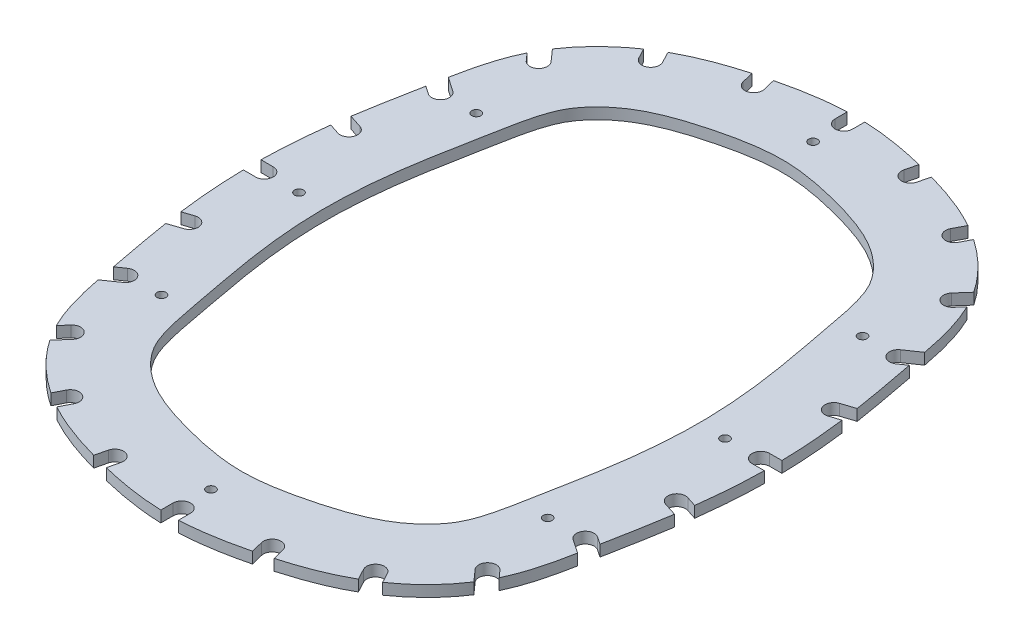
SolidWorks part; units mm, degrees
ref_plane "Front Plane" through (0, 0, 0) normal (0, 0, 1) x (1, 0, 0)
ref_plane "Top Plane" through (0, 0, 0) normal (0, 1, 0) x (1, 0, 0)
ref_plane "Right Plane" through (0, 0, 0) normal (1, 0, 0) x (0, 0, -1)
sketch "MainControlPoints" plane through (0, 0, 0) normal (0, 1, 0) x (1, 0, 0)
  line L1 (0, 188.5) -> (0, 0) construction
  line L2 (-44.5, 181.8105) -> (44.5, 181.8105) construction
  line L9 (-141, 0) -> (141, 0) construction
  line L10 (-86.25, 165.0195) -> (86.25, 165.0195) construction
  line L11 (-117.5, 132.6399) -> (117.5, 132.6399) construction
  line L12 (-130, 89.4108) -> (130, 89.4108) construction
  line L13 (-137.75, 45.0832) -> (137.75, 45.0832) construction
  spline S0 degree 3 poles (-44.8235, 182.8439) (0, 191.3281) (44.8235, 182.8439) (87.706, 168.1591) (121.8523, 134.6364) (129.8847, 89.1344) (138.6218, 45.2258) (142.1917, 0) (138.6218, -45.2258) (129.8847, -89.1344) (121.8523, -134.6364) (87.706, -168.1591) (44.8235, -182.8439) (0, -191.3281) (-44.8235, -182.8439) (-87.706, -168.1591) (-121.8523, -134.6364) (-129.8847, -89.1344) (-138.6218, -45.2258) (-142.1917, 0) (-138.6218, 45.2258) (-129.8847, 89.1344) (-121.8523, 134.6364) (-87.706, 168.1591) (-44.8235, 182.8439) (0, 191.3281) (44.8235, 182.8439) knots -0.124907 -0.083272 -0.041636 0 0.041636 0.083272 0.124907 0.166543 0.208179 0.25 0.291821 0.333457 0.375093 0.416728 0.458364 0.5 0.541636 0.583272 0.624907 0.666543 0.708179 0.75 0.791821 0.833457 0.875093 0.916728 0.958364 1 1.041636 1.083272 1.124907 only from (0, 188.5) to (0, 188.5)
  point P4 (0, 181.8105)
  point P7 (0, 0)
  point P8 (141, 0)
  point P9 (-141, 0)
  point P11 (44.5, 181.8105)
  point P14 (86.25, 165.0195)
  point P15 (0, 165.0195)
  point P16 (117.5, 132.6399)
  point P17 (130, 89.4108)
  point P18 (-44.5, 181.8105)
  point P19 (-86.25, 165.0195)
  point P20 (-117.5, 132.6399)
  point P23 (0, 132.6399)
  point P24 (137.75, 45.0832)
  point P25 (-130, 89.4108)
  point P26 (-137.75, 45.0832)
  point P27 (0, 188.5)
  point P30 (0, 89.4108)
  point P33 (0, 45.0832)
  point P34 (137.75, -45.0832)
  point P35 (130, -89.4108)
  point P36 (117.5, -132.6399)
  point P37 (86.25, -165.0195)
  point P38 (44.5, -181.8105)
  point P39 (0, -188.5)
  point P40 (-44.5, -181.8105)
  point P41 (-86.25, -165.0195)
  point P42 (-117.5, -132.6399)
  point P43 (-130, -89.4108)
  point P44 (-137.75, -45.0832)
  dimension "D3" = 282
  dimension "D2" = 188.5
  dimension "D5" = 45
  dimension "D6" = 45
  dimension "D1" = 89
  dimension "D4" = 172.5
  dimension "D7" = 45
  dimension "D8" = 235
  dimension "D9" = 45
  dimension "D10" = 260
  dimension "D11" = 45
  dimension "D12" = 275.5
ref_axis "Axis1" through (0, 0, -188.5) along (0, 1, 0)
ref_axis "Axis2" through (44.5, 0, -181.8105) along (0, 1, 0)
ref_axis "Axis3" through (86.25, 0, -165.0195) along (0, 1, 0)
ref_axis "Axis4" through (117.5, 0, -132.6399) along (0, 1, 0)
ref_axis "Axis5" through (130, 0, -89.4108) along (0, 1, 0)
ref_axis "Axis6" through (137.75, 0, -45.0832) along (0, 1, 0)
ref_axis "Axis7" through (141, 0, 0) along (0, 1, 0)
ref_axis "Axis8" through (137.75, 0, 45.0832) along (0, 1, 0)
ref_axis "Axis9" through (130, 0, 89.4108) along (0, 1, 0)
ref_axis "Axis10" through (117.5, 0, 132.6399) along (0, 1, 0)
ref_axis "Axis11" through (86.25, 0, 165.0195) along (0, 1, 0)
ref_axis "Axis12" through (44.5, 0, 181.8105) along (0, 1, 0)
ref_axis "Axis13" through (0, 0, 188.5) along (0, 1, 0)
ref_axis "Axis14" through (-44.5, 0, 181.8105) along (0, 1, 0)
ref_axis "Axis15" through (-86.25, 0, 165.0195) along (0, 1, 0)
ref_axis "Axis16" through (-117.5, 0, 132.6399) along (0, 1, 0)
ref_axis "Axis17" through (-130, 0, 89.4108) along (0, 1, 0)
ref_axis "Axis18" through (-137.75, 0, 45.0832) along (0, 1, 0)
ref_axis "Axis19" through (-141, 0, 0) along (0, 1, 0)
ref_axis "Axis20" through (-137.75, 0, -45.0832) along (0, 1, 0)
ref_axis "Axis21" through (-130, 0, -89.4108) along (0, 1, 0)
ref_axis "Axis22" through (-117.5, 0, -132.6399) along (0, 1, 0)
ref_axis "Axis23" through (-86.25, 0, -165.0195) along (0, 1, 0)
ref_axis "Axis24" through (-44.5, 0, -181.8105) along (0, 1, 0)
sketch "Sketch3" plane through (0, 0, 0) normal (0, 1, 0) x (1, 0, 0)
  spline S2 degree 3 poles (44.8235, 182.8439) (0, 191.3281) (-44.8235, 182.8439) (-87.706, 168.1591) (-121.8523, 134.6364) (-129.8847, 89.1344) (-138.6218, 45.2258) (-142.1917, 0) (-138.6218, -45.2258) (-129.8847, -89.1344) (-121.8523, -134.6364) (-87.706, -168.1591) (-44.8235, -182.8439) (0, -191.3281) (44.8235, -182.8439) (87.706, -168.1591) (121.8523, -134.6364) (129.8847, -89.1344) (138.6218, -45.2258) (142.1917, 0) (138.6218, 45.2258) (129.8847, 89.1344) (121.8523, 134.6364) (87.706, 168.1591) (44.8235, 182.8439) (0, 191.3281) (-44.8235, 182.8439) knots -0.124907 -0.083272 -0.041636 0 0.041636 0.083272 0.124907 0.166543 0.208179 0.25 0.291821 0.333457 0.375093 0.416728 0.458364 0.5 0.541636 0.583272 0.624907 0.666543 0.708179 0.75 0.791821 0.833457 0.875093 0.916728 0.958364 1 1.041636 1.083272 1.124907 only from (0, 188.5) to (0, 188.5)
  spline S3 degree 3 poles (44.8235, 182.8439) (0, 191.3281) (-44.8235, 182.8439) (-87.706, 168.1591) (-121.8523, 134.6364) (-129.8847, 89.1344) (-138.6218, 45.2258) (-142.1917, 0) (-138.6218, -45.2258) (-129.8847, -89.1344) (-121.8523, -134.6364) (-87.706, -168.1591) (-44.8235, -182.8439) (0, -191.3281) (44.8235, -182.8439) (87.706, -168.1591) (121.8523, -134.6364) (129.8847, -89.1344) (138.6218, -45.2258) (142.1917, 0) (138.6218, 45.2258) (129.8847, 89.1344) (121.8523, 134.6364) (87.706, 168.1591) (44.8235, 182.8439) (0, 191.3281) (-44.8235, 182.8439) knots -0.124907 -0.083272 -0.041636 0 0.041636 0.083272 0.124907 0.166543 0.208179 0.25 0.291821 0.333457 0.375093 0.416728 0.458364 0.5 0.541636 0.583272 0.624907 0.666543 0.708179 0.75 0.791821 0.833457 0.875093 0.916728 0.958364 1 1.041636 1.083272 1.124907 only from (0, 188.5) to (0, 188.5)
  dimension "D1" = 0
extrude "MainBody" add sketch "Sketch3" along normal blind 6.35
sketch "Sketch13" plane through (0, 6.35, 0) normal (0, 1, 0) x (1, 0, 0)
  spline S2 degree 3 poles (-0.0923, -195.5) (5.9061, -195.5) (11.7392, -195.085) (23.2981, -193.6453) (29.0237, -192.6199) (37.5559, -190.7615) (40.3905, -190.0886) (46.0447, -188.657) (48.8649, -187.9023) (53.0829, -186.6998) (54.4867, -186.2866) (57.2893, -185.4316) (58.6882, -184.9896) (62.8604, -183.6197) (65.6138, -182.6462) (73.7714, -179.5048) (79.0728, -177.1157) (86.7462, -172.933) (89.2575, -171.4385) (92.9463, -169.029) (94.1653, -168.1965) (96.5575, -166.4889) (97.7326, -165.6128) (101.1944, -162.9177) (103.4182, -161.032) (107.6923, -157.0772) (109.7427, -155.0081) (112.678, -151.7562) (113.633, -150.6474) (115.0284, -148.9451) (115.4873, -148.3711) (116.3925, -147.2097) (116.8393, -146.6213) (119.0306, -143.6582) (120.6466, -141.2209) (123.5916, -136.206) (124.9153, -133.6259) (127.2923, -128.3337) (128.3485, -125.623) (129.7723, -121.4785) (130.2202, -120.084) (131.0691, -117.272) (131.4694, -115.8571) (132.6042, -111.6095) (133.2755, -108.7656) (134.5145, -103.0626) (135.0819, -100.2036) (136.1775, -94.48) (136.707, -91.6156) (138.3251, -83.0265) (139.4215, -77.303) (141.5293, -65.8438) (142.5403, -60.108) (143.9035, -51.4821) (144.3323, -48.6031) (145.1247, -42.8358) (145.4885, -39.9475) (147.1362, -25.4811) (147.9101, -13.8294) (148.003, -0.6092) (148.0024, 0.8623) (147.9792, 3.8019) (147.9568, 5.2701) (147.8578, 9.6699) (147.7498, 12.5969) (147.3068, 21.3604) (146.8533, 27.1792) (145.6651, 38.7754) (144.9284, 44.5524) (143.2126, 56.0705) (142.2389, 61.8124) (140.1775, 73.2794) (139.0901, 79.0044) (137.4645, 87.5929) (136.9262, 90.4562) (135.8531, 96.1835) (135.3122, 99.0464) (133.5786, 107.6189) (132.2779, 113.3124) (130.1353, 120.3529) (129.6824, 121.7514) (128.7233, 124.5187) (128.2169, 125.8886) (126.6073, 129.9525) (125.4138, 132.6004) (122.7385, 137.7496) (121.2544, 140.2496) (118.8215, 143.8945) (117.9761, 145.0919) (116.2177, 147.4523) (115.3033, 148.6168) (112.4942, 152.0199) (110.5242, 154.1827) (106.4077, 158.3162) (104.2612, 160.2869) (99.8013, 164.0465) (97.4878, 165.8355) (93.8939, 168.384) (92.6724, 169.2128) (90.2027, 170.8151) (88.9554, 171.5879) (82.6598, 175.3171) (77.4348, 177.8708) (66.7035, 182.3362) (61.1969, 184.2476) (54.1978, 186.3725) (52.791, 186.7846) (49.9736, 187.5842) (48.5634, 187.9716) (44.3294, 189.1029) (41.5021, 189.818) (33.0032, 191.8167) (27.3144, 192.953) (15.8708, 194.6608) (10.1162, 195.2328) (1.4182, 195.5241) (-1.4925, 195.5238) (-7.3372, 195.3237) (-10.2708, 195.1267) (-14.6866, 194.6996) (-16.1609, 194.5352) (-19.0943, 194.1679) (-20.556, 193.9647) (-24.9277, 193.3015) (-27.824, 192.7881) (-36.4681, 191.071) (-42.1715, 189.6926) (-53.5026, 186.6371) (-59.1262, 184.9441) (-66.0624, 182.4605) (-67.445, 181.9454) (-70.1997, 180.8739) (-71.5737, 180.3168) (-75.6639, 178.5832) (-78.3432, 177.3468) (-83.5935, 174.6901) (-86.1644, 173.2698) (-91.1858, 170.2243) (-93.6357, 168.5985) (-97.2169, 166.0005) (-98.395, 165.108) (-100.7189, 163.2682) (-101.8655, 162.32) (-105.2234, 159.4186) (-107.3637, 157.4004) (-111.4418, 153.191) (-113.3796, 150.9998) (-117.0378, 146.4319) (-118.7583, 144.0551) (-121.1568, 140.3344) (-121.9259, 139.0681) (-123.0304, 137.1268) (-123.3898, 136.4736) (-124.087, 135.1618) (-124.4255, 134.5022) (-126.0692, 131.1868) (-127.2294, 128.4785) (-130.3408, 120.2205) (-131.9223, 114.5371) (-134.5909, 102.9918) (-135.6643, 97.1921) (-137.8355, 85.5987) (-138.9477, 79.8043) (-141.1029, 68.2094) (-142.1451, 62.4088) (-143.5618, 53.6948) (-144.0097, 50.788) (-144.8419, 44.9686) (-145.2255, 42.056) (-146.97, 27.4776) (-147.815, 15.7657) (-148.0521, -1.8942) (-147.9538, -7.7967) (-147.4225, -19.6316) (-146.9909, -25.5639) (-146.1143, -34.4827) (-145.7838, -37.4592) (-145.0527, -43.3941) (-144.6515, -46.3556) (-143.3516, -55.2244) (-142.36, -61.1163) (-140.253, -72.8796) (-139.1381, -78.7512) (-137.4708, -87.5593) (-136.9189, -90.496) (-135.8181, -96.3698) (-135.2627, -99.3053) (-133.4794, -108.0788) (-132.1352, -113.8842) (-129.4893, -122.4151) (-128.5024, -125.2292) (-126.8117, -129.3912) (-126.2131, -130.7686) (-125.2553, -132.818) (-124.9263, -133.498) (-124.2516, -134.843) (-123.9056, -135.5092) (-122.1306, -138.8075) (-120.5688, -141.343) (-117.1925, -146.2303) (-115.378, -148.582) (-111.5149, -153.1153) (-109.4647, -155.2983) (-105.1449, -159.494) (-102.9036, -161.4797) (-95.9543, -167.1259) (-91.0211, -170.4758) (-84.4967, -174.1698) (-83.1716, -174.8856) (-80.5028, -176.2632) (-79.1594, -176.925) (-75.1047, -178.8358) (-72.3686, -180.0105) (-64.0786, -183.2871) (-58.4429, -185.1422) (-49.8888, -187.6214) (-47.0211, -188.3984) (-41.2605, -189.8765) (-38.3664, -190.5739) (-32.5429, -191.862) (-29.6099, -192.4531) (-23.735, -193.4975) (-20.7901, -193.9515) (-14.8831, -194.699) (-11.9208, -194.9924) (-7.4624, -195.2928) (-5.9738, -195.3696) (-3.7367, -195.4473) (-2.6172, -195.4768) (-1.3092, -195.4942) (-0.6548, -195.4985) (-0.3742, -195.4995) (-0.1871, -195.4999) (-0.0923, -195.5) (5.9061, -195.5) (11.7392, -195.085) knots -0.000244 -0.000244 0 0 0.015625 0.015625 0.03125 0.03125 0.039063 0.039063 0.046875 0.046875 0.050781 0.050781 0.054688 0.054688 0.0625 0.0625 0.078125 0.078125 0.085938 0.085938 0.089844 0.089844 0.09375 0.09375 0.101563 0.101563 0.109375 0.109375 0.113281 0.113281 0.115234 0.115234 0.117188 0.117188 0.125 0.125 0.132813 0.132813 0.140625 0.140625 0.144531 0.144531 0.148438 0.148438 0.15625 0.15625 0.164063 0.164063 0.171875 0.171875 0.1875 0.1875 0.203125 0.203125 0.210938 0.210938 0.21875 0.21875 0.25 0.25 0.253906 0.253906 0.257813 0.257813 0.265625 0.265625 0.28125 0.28125 0.296875 0.296875 0.3125 0.3125 0.328125 0.328125 0.335938 0.335938 0.34375 0.34375 0.359375 0.359375 0.363281 0.363281 0.367188 0.367188 0.375 0.375 0.382813 0.382813 0.386719 0.386719 0.390625 0.390625 0.398438 0.398438 0.40625 0.40625 0.414063 0.414063 0.417969 0.417969 0.421875 0.421875 0.4375 0.4375 0.453125 0.453125 0.457031 0.457031 0.460938 0.460938 0.46875 0.46875 0.484375 0.484375 0.5 0.5 0.507813 0.507813 0.515625 0.515625 0.519531 0.519531 0.523438 0.523438 0.53125 0.53125 0.546875 0.546875 0.5625 0.5625 0.566406 0.566406 0.570313 0.570313 0.578125 0.578125 0.585938 0.585938 0.59375 0.59375 0.597656 0.597656 0.601563 0.601563 0.609375 0.609375 0.617188 0.617188 0.625 0.625 0.628906 0.628906 0.630859 0.630859 0.632813 0.632813 0.640625 0.640625 0.65625 0.65625 0.671875 0.671875 0.6875 0.6875 0.703125 0.703125 0.710937 0.710937 0.71875 0.71875 0.75 0.75 0.765625 0.765625 0.78125 0.78125 0.789062 0.789062 0.796875 0.796875 0.8125 0.8125 0.828125 0.828125 0.835937 0.835937 0.84375 0.84375 0.859375 0.859375 0.867187 0.867187 0.871094 0.871094 0.873047 0.873047 0.875 0.875 0.882812 0.882812 0.890625 0.890625 0.898437 0.898437 0.90625 0.90625 0.921875 0.921875 0.925781 0.925781 0.929687 0.929687 0.9375 0.9375 0.953125 0.953125 0.960937 0.960937 0.96875 0.96875 0.976562 0.976562 0.984375 0.984375 0.992188 0.992188 0.996094 0.996094 0.998047 0.999023 0.999512 0.999756 0.999756 1 1 1.015625 1.015625 1.03125 only from (0, -195.5) to (0, -195.5)
  spline S3 degree 3 poles (-0.0923, -195.5) (5.9061, -195.5) (11.7392, -195.085) (23.2981, -193.6453) (29.0237, -192.6199) (37.5559, -190.7615) (40.3905, -190.0886) (46.0447, -188.657) (48.8649, -187.9023) (53.0829, -186.6998) (54.4867, -186.2866) (57.2893, -185.4316) (58.6882, -184.9896) (62.8604, -183.6197) (65.6138, -182.6462) (73.7714, -179.5048) (79.0728, -177.1157) (86.7462, -172.933) (89.2575, -171.4385) (92.9463, -169.029) (94.1653, -168.1965) (96.5575, -166.4889) (97.7326, -165.6128) (101.1944, -162.9177) (103.4182, -161.032) (107.6923, -157.0772) (109.7427, -155.0081) (112.678, -151.7562) (113.633, -150.6474) (115.0284, -148.9451) (115.4873, -148.3711) (116.3925, -147.2097) (116.8393, -146.6213) (119.0306, -143.6582) (120.6466, -141.2209) (123.5916, -136.206) (124.9153, -133.6259) (127.2923, -128.3337) (128.3485, -125.623) (129.7723, -121.4785) (130.2202, -120.084) (131.0691, -117.272) (131.4694, -115.8571) (132.6042, -111.6095) (133.2755, -108.7656) (134.5145, -103.0626) (135.0819, -100.2036) (136.1775, -94.48) (136.707, -91.6156) (138.3251, -83.0265) (139.4215, -77.303) (141.5293, -65.8438) (142.5403, -60.108) (143.9035, -51.4821) (144.3323, -48.6031) (145.1247, -42.8358) (145.4885, -39.9475) (147.1362, -25.4811) (147.9101, -13.8294) (148.003, -0.6092) (148.0024, 0.8623) (147.9792, 3.8019) (147.9568, 5.2701) (147.8578, 9.6699) (147.7498, 12.5969) (147.3068, 21.3604) (146.8533, 27.1792) (145.6651, 38.7754) (144.9284, 44.5524) (143.2126, 56.0705) (142.2389, 61.8124) (140.1775, 73.2794) (139.0901, 79.0044) (137.4645, 87.5929) (136.9262, 90.4562) (135.8531, 96.1835) (135.3122, 99.0464) (133.5786, 107.6189) (132.2779, 113.3124) (130.1353, 120.3529) (129.6824, 121.7514) (128.7233, 124.5187) (128.2169, 125.8886) (126.6073, 129.9525) (125.4138, 132.6004) (122.7385, 137.7496) (121.2544, 140.2496) (118.8215, 143.8945) (117.9761, 145.0919) (116.2177, 147.4523) (115.3033, 148.6168) (112.4942, 152.0199) (110.5242, 154.1827) (106.4077, 158.3162) (104.2612, 160.2869) (99.8013, 164.0465) (97.4878, 165.8355) (93.8939, 168.384) (92.6724, 169.2128) (90.2027, 170.8151) (88.9554, 171.5879) (82.6598, 175.3171) (77.4348, 177.8708) (66.7035, 182.3362) (61.1969, 184.2476) (54.1978, 186.3725) (52.791, 186.7846) (49.9736, 187.5842) (48.5634, 187.9716) (44.3294, 189.1029) (41.5021, 189.818) (33.0032, 191.8167) (27.3144, 192.953) (15.8708, 194.6608) (10.1162, 195.2328) (1.4182, 195.5241) (-1.4925, 195.5238) (-7.3372, 195.3237) (-10.2708, 195.1267) (-14.6866, 194.6996) (-16.1609, 194.5352) (-19.0943, 194.1679) (-20.556, 193.9647) (-24.9277, 193.3015) (-27.824, 192.7881) (-36.4681, 191.071) (-42.1715, 189.6926) (-53.5026, 186.6371) (-59.1262, 184.9441) (-66.0624, 182.4605) (-67.445, 181.9454) (-70.1997, 180.8739) (-71.5737, 180.3168) (-75.6639, 178.5832) (-78.3432, 177.3468) (-83.5935, 174.6901) (-86.1644, 173.2698) (-91.1858, 170.2243) (-93.6357, 168.5985) (-97.2169, 166.0005) (-98.395, 165.108) (-100.7189, 163.2682) (-101.8655, 162.32) (-105.2234, 159.4186) (-107.3637, 157.4004) (-111.4418, 153.191) (-113.3796, 150.9998) (-117.0378, 146.4319) (-118.7583, 144.0551) (-121.1568, 140.3344) (-121.9259, 139.0681) (-123.0304, 137.1268) (-123.3898, 136.4736) (-124.087, 135.1618) (-124.4255, 134.5022) (-126.0692, 131.1868) (-127.2294, 128.4785) (-130.3408, 120.2205) (-131.9223, 114.5371) (-134.5909, 102.9918) (-135.6643, 97.1921) (-137.8355, 85.5987) (-138.9477, 79.8043) (-141.1029, 68.2094) (-142.1451, 62.4088) (-143.5618, 53.6948) (-144.0097, 50.788) (-144.8419, 44.9686) (-145.2255, 42.056) (-146.97, 27.4776) (-147.815, 15.7657) (-148.0521, -1.8942) (-147.9538, -7.7967) (-147.4225, -19.6316) (-146.9909, -25.5639) (-146.1143, -34.4827) (-145.7838, -37.4592) (-145.0527, -43.3941) (-144.6515, -46.3556) (-143.3516, -55.2244) (-142.36, -61.1163) (-140.253, -72.8796) (-139.1381, -78.7512) (-137.4708, -87.5593) (-136.9189, -90.496) (-135.8181, -96.3698) (-135.2627, -99.3053) (-133.4794, -108.0788) (-132.1352, -113.8842) (-129.4893, -122.4151) (-128.5024, -125.2292) (-126.8117, -129.3912) (-126.2131, -130.7686) (-125.2553, -132.818) (-124.9263, -133.498) (-124.2516, -134.843) (-123.9056, -135.5092) (-122.1306, -138.8075) (-120.5688, -141.343) (-117.1925, -146.2303) (-115.378, -148.582) (-111.5149, -153.1153) (-109.4647, -155.2983) (-105.1449, -159.494) (-102.9036, -161.4797) (-95.9543, -167.1259) (-91.0211, -170.4758) (-84.4967, -174.1698) (-83.1716, -174.8856) (-80.5028, -176.2632) (-79.1594, -176.925) (-75.1047, -178.8358) (-72.3686, -180.0105) (-64.0786, -183.2871) (-58.4429, -185.1422) (-49.8888, -187.6214) (-47.0211, -188.3984) (-41.2605, -189.8765) (-38.3664, -190.5739) (-32.5429, -191.862) (-29.6099, -192.4531) (-23.735, -193.4975) (-20.7901, -193.9515) (-14.8831, -194.699) (-11.9208, -194.9924) (-7.4624, -195.2928) (-5.9738, -195.3696) (-3.7367, -195.4473) (-2.6172, -195.4768) (-1.3092, -195.4942) (-0.6548, -195.4985) (-0.3742, -195.4995) (-0.1871, -195.4999) (-0.0923, -195.5) (5.9061, -195.5) (11.7392, -195.085) knots -0.000244 -0.000244 0 0 0.015625 0.015625 0.03125 0.03125 0.039063 0.039063 0.046875 0.046875 0.050781 0.050781 0.054688 0.054688 0.0625 0.0625 0.078125 0.078125 0.085938 0.085938 0.089844 0.089844 0.09375 0.09375 0.101563 0.101563 0.109375 0.109375 0.113281 0.113281 0.115234 0.115234 0.117188 0.117188 0.125 0.125 0.132813 0.132813 0.140625 0.140625 0.144531 0.144531 0.148438 0.148438 0.15625 0.15625 0.164063 0.164063 0.171875 0.171875 0.1875 0.1875 0.203125 0.203125 0.210938 0.210938 0.21875 0.21875 0.25 0.25 0.253906 0.253906 0.257813 0.257813 0.265625 0.265625 0.28125 0.28125 0.296875 0.296875 0.3125 0.3125 0.328125 0.328125 0.335938 0.335938 0.34375 0.34375 0.359375 0.359375 0.363281 0.363281 0.367188 0.367188 0.375 0.375 0.382813 0.382813 0.386719 0.386719 0.390625 0.390625 0.398438 0.398438 0.40625 0.40625 0.414063 0.414063 0.417969 0.417969 0.421875 0.421875 0.4375 0.4375 0.453125 0.453125 0.457031 0.457031 0.460938 0.460938 0.46875 0.46875 0.484375 0.484375 0.5 0.5 0.507813 0.507813 0.515625 0.515625 0.519531 0.519531 0.523438 0.523438 0.53125 0.53125 0.546875 0.546875 0.5625 0.5625 0.566406 0.566406 0.570313 0.570313 0.578125 0.578125 0.585938 0.585938 0.59375 0.59375 0.597656 0.597656 0.601563 0.601563 0.609375 0.609375 0.617188 0.617188 0.625 0.625 0.628906 0.628906 0.630859 0.630859 0.632813 0.632813 0.640625 0.640625 0.65625 0.65625 0.671875 0.671875 0.6875 0.6875 0.703125 0.703125 0.710937 0.710937 0.71875 0.71875 0.75 0.75 0.765625 0.765625 0.78125 0.78125 0.789062 0.789062 0.796875 0.796875 0.8125 0.8125 0.828125 0.828125 0.835937 0.835937 0.84375 0.84375 0.859375 0.859375 0.867187 0.867187 0.871094 0.871094 0.873047 0.873047 0.875 0.875 0.882812 0.882812 0.890625 0.890625 0.898437 0.898437 0.90625 0.90625 0.921875 0.921875 0.925781 0.925781 0.929687 0.929687 0.9375 0.9375 0.953125 0.953125 0.960937 0.960937 0.96875 0.96875 0.976562 0.976562 0.984375 0.984375 0.992188 0.992188 0.996094 0.996094 0.998047 0.999023 0.999512 0.999756 0.999756 1 1 1.015625 1.015625 1.03125 only from (0, -195.5) to (0, -195.5)
  dimension "D1" = 7
extrude "Extrude2Lip" add sketch "Sketch13" against normal up to surface (6.35 mm away)
sketch "Sketch14" plane through (0, 6.35, 0) normal (0, 1, 0) x (1, 0, 0)
  line L0 (-5, 188.5) -> (-5, 199.1798)
  line L1 (-5, 199.1798) -> (5, 199.1798)
  line L2 (5, 199.1798) -> (5, 188.5)
  line L9 (0, 188.5) -> (0, 199.1798) construction
  line L13 (-5, 188.5) -> (5, 188.5) construction
  line L20 (39.6434, 182.9992) -> (42.1824, 193.3728)
  line L21 (42.1824, 193.3728) -> (51.8957, 190.9953)
  line L22 (0, 0) -> (44.5, 181.8105) construction
  line L23 (0, 0) -> (86.25, 165.0195) construction
  line L24 (0, 0) -> (117.5, 132.6399) construction
  line L25 (0, 0) -> (130, 89.4108) construction
  line L26 (0, 0) -> (137.75, 45.0832) construction
  line L27 (0, 0) -> (141, 0.3435) construction
  line L28 (0, 0) -> (0, 188.5) construction
  line L29 (51.8957, 190.9953) -> (49.3566, 180.6217)
  line L30 (44.5, 181.8105) -> (47.039, 192.1841) construction
  line L31 (39.6434, 182.9992) -> (49.3566, 180.6217) construction
  line L32 (81.8188, 167.3355) -> (86.7658, 176.8005)
  line L33 (86.7658, 176.8005) -> (95.6283, 172.1684)
  line L34 (95.6283, 172.1684) -> (90.6812, 162.7034)
  line L35 (86.25, 165.0195) -> (91.197, 174.4844) construction
  line L36 (81.8188, 167.3355) -> (90.6812, 162.7034) construction
  line L37 (113.7573, 135.9554) -> (125.8891, 149.6503)
  line L38 (125.8891, 149.6503) -> (133.3744, 143.0193)
  line L39 (133.3744, 143.0193) -> (121.2427, 129.3244)
  line L40 (117.5, 132.6399) -> (129.6317, 146.3348) construction
  line L41 (113.7573, 135.9554) -> (121.2427, 129.3244) construction
  line L42 (127.1666, 93.5305) -> (142.2527, 103.9064)
  line L43 (142.2527, 103.9064) -> (147.9195, 95.667)
  line L44 (147.9195, 95.667) -> (132.8334, 85.2912)
  line L45 (130, 89.4108) -> (145.0861, 99.7867) construction
  line L46 (127.1666, 93.5305) -> (132.8334, 85.2912) construction
  line L47 (136.1948, 49.8352) -> (153.5963, 55.5304)
  line L48 (153.5963, 55.5304) -> (156.7067, 46.0265)
  line L49 (156.7067, 46.0265) -> (139.3052, 40.3312)
  line L50 (137.75, 45.0832) -> (155.1515, 50.7784) construction
  line L51 (136.1948, 49.8352) -> (139.3052, 40.3312) construction
  line L52 (140.9878, 5.3435) -> (159.2975, 5.3881)
  line L53 (159.2975, 5.3881) -> (159.3219, -4.6119)
  line L54 (159.3219, -4.6119) -> (141.0122, -4.6565)
  line L55 (141, 0.3435) -> (159.3097, 0.3881) construction
  line L56 (140.9878, 5.3435) -> (141.0122, -4.6565) construction
  line L57 (-140.9878, 5.3435) -> (-141.0122, -4.6565) construction
  line L58 (-141, 0.3435) -> (-159.3097, 0.3881) construction
  line L59 (-136.1948, 49.8352) -> (-139.3052, 40.3312) construction
  line L60 (-137.75, 45.0832) -> (-155.1515, 50.7784) construction
  line L61 (-127.1666, 93.5305) -> (-132.8334, 85.2912) construction
  line L62 (-130, 89.4108) -> (-145.0861, 99.7867) construction
  line L63 (-113.7573, 135.9554) -> (-121.2427, 129.3244) construction
  line L64 (-117.5, 132.6399) -> (-129.6317, 146.3348) construction
  line L65 (-81.8188, 167.3355) -> (-90.6812, 162.7034) construction
  line L66 (-86.25, 165.0195) -> (-91.197, 174.4844) construction
  line L67 (-39.6434, 182.9992) -> (-49.3566, 180.6217) construction
  line L68 (-44.5, 181.8105) -> (-47.039, 192.1841) construction
  line L69 (-159.3219, -4.6119) -> (-141.0122, -4.6565)
  line L70 (-159.2975, 5.3881) -> (-159.3219, -4.6119)
  line L71 (-140.9878, 5.3435) -> (-159.2975, 5.3881)
  line L72 (-156.7067, 46.0265) -> (-139.3052, 40.3312)
  line L73 (-153.5963, 55.5304) -> (-156.7067, 46.0265)
  line L74 (-136.1948, 49.8352) -> (-153.5963, 55.5304)
  line L75 (-147.9195, 95.667) -> (-132.8334, 85.2912)
  line L76 (-142.2527, 103.9064) -> (-147.9195, 95.667)
  line L77 (-127.1666, 93.5305) -> (-142.2527, 103.9064)
  line L78 (-133.3744, 143.0193) -> (-121.2427, 129.3244)
  line L79 (-125.8891, 149.6503) -> (-133.3744, 143.0193)
  line L80 (-113.7573, 135.9554) -> (-125.8891, 149.6503)
  line L81 (-95.6283, 172.1684) -> (-90.6812, 162.7034)
  line L82 (-86.7658, 176.8005) -> (-95.6283, 172.1684)
  line L83 (-81.8188, 167.3355) -> (-86.7658, 176.8005)
  line L84 (-51.8957, 190.9953) -> (-49.3566, 180.6217)
  line L85 (-42.1824, 193.3728) -> (-51.8957, 190.9953)
  line L86 (-39.6434, 182.9992) -> (-42.1824, 193.3728)
  line L87 (-43.6136, -182.0251) -> (-46.1021, -192.411) construction
  line L88 (-38.7512, -183.1902) -> (-48.476, -180.8601) construction
  line L89 (-85.4449, -165.4378) -> (-90.3457, -174.9267) construction
  line L90 (-81.0024, -167.7322) -> (-89.8874, -163.1433) construction
  line L91 (-116.8523, -133.2108) -> (-128.9172, -146.9647) construction
  line L92 (-113.0935, -136.508) -> (-120.6111, -129.9136) construction
  line L93 (-129.5628, -90.0432) -> (-144.5981, -100.4924) construction
  line L94 (-126.7093, -94.149) -> (-132.4163, -85.9374) construction
  line L95 (-137.5287, -45.7539) -> (-154.9022, -51.5338) construction
  line L96 (-135.9503, -50.4982) -> (-139.1071, -41.0095) construction
  line L97 (136.436, -49.171) -> (139.5001, -39.652) construction
  line L98 (137.968, -44.4115) -> (155.3971, -50.0219) construction
  line L99 (127.6208, -92.9098) -> (133.2474, -84.6429) construction
  line L100 (130.4341, -88.7763) -> (145.5706, -99.0786) construction
  line L101 (114.4184, -135.3995) -> (121.8714, -128.7321) construction
  line L102 (118.1449, -132.0658) -> (130.3432, -145.7014) construction
  line L103 (82.6331, -166.9349) -> (91.4729, -162.2596) construction
  line L104 (87.053, -164.5972) -> (92.0461, -174.038) construction
  line L105 (40.5346, -182.8038) -> (50.2361, -180.3791) construction
  line L106 (45.3853, -181.5915) -> (47.9749, -191.9526) construction
  line L107 (-4.0815, -188.5221) -> (5.9184, -188.4734) construction
  line L108 (0.9185, -188.4978) -> (0.9705, -199.1775) construction
  line L109 (-38.7512, -183.1902) -> (-41.2397, -193.576)
  line L110 (-41.2397, -193.576) -> (-50.9644, -191.2459)
  line L111 (-50.9644, -191.2459) -> (-48.476, -180.8601)
  line L112 (-81.0024, -167.7322) -> (-85.9033, -177.2212)
  line L113 (-85.9033, -177.2212) -> (-94.7882, -172.6323)
  line L114 (-94.7882, -172.6323) -> (-89.8874, -163.1433)
  line L115 (-113.0935, -136.508) -> (-125.1584, -150.2619)
  line L116 (-125.1584, -150.2619) -> (-132.676, -143.6675)
  line L117 (-132.676, -143.6675) -> (-120.6111, -129.9136)
  line L118 (-126.7093, -94.149) -> (-141.7447, -104.5983)
  line L119 (-141.7447, -104.5983) -> (-147.4516, -96.3866)
  line L120 (-147.4516, -96.3866) -> (-132.4163, -85.9374)
  line L121 (-135.9503, -50.4982) -> (-153.3239, -56.2781)
  line L122 (-153.3239, -56.2781) -> (-156.4806, -46.7895)
  line L123 (-156.4806, -46.7895) -> (-139.1071, -41.0095)
  line L124 (156.9292, -45.2624) -> (139.5001, -39.652)
  line L125 (153.865, -54.7813) -> (156.9292, -45.2624)
  line L126 (136.436, -49.171) -> (153.865, -54.7813)
  line L127 (148.3839, -94.9451) -> (133.2474, -84.6429)
  line L128 (142.7573, -103.212) -> (148.3839, -94.9451)
  line L129 (127.6208, -92.9098) -> (142.7573, -103.212)
  line L130 (134.0697, -142.3677) -> (121.8714, -128.7321)
  line L131 (126.6167, -149.0351) -> (134.0697, -142.3677)
  line L132 (114.4184, -135.3995) -> (126.6167, -149.0351)
  line L133 (96.466, -171.7004) -> (91.4729, -162.2596)
  line L134 (87.6262, -176.3756) -> (96.466, -171.7004)
  line L135 (82.6331, -166.9349) -> (87.6262, -176.3756)
  line L136 (52.8257, -190.7402) -> (50.2361, -180.3791)
  line L137 (43.1241, -193.1649) -> (52.8257, -190.7402)
  line L138 (40.5346, -182.8038) -> (43.1241, -193.1649)
  line L139 (5.9704, -199.1531) -> (5.9184, -188.4734)
  line L140 (-4.0294, -199.2018) -> (5.9704, -199.1531)
  line L141 (-4.0815, -188.5221) -> (-4.0294, -199.2018)
  arc A0 (-5, 188.5) -> (5, 188.5) centre (0, 188.5) ccw
  arc A1 (39.6434, 182.9992) -> (49.3566, 180.6217) centre (44.5, 181.8105) ccw
  arc A2 (81.8188, 167.3355) -> (90.6812, 162.7034) centre (86.25, 165.0195) ccw
  arc A3 (113.7573, 135.9554) -> (121.2427, 129.3244) centre (117.5, 132.6399) ccw
  arc A4 (127.1666, 93.5305) -> (132.8334, 85.2912) centre (130, 89.4108) ccw
  arc A5 (136.1948, 49.8352) -> (139.3052, 40.3312) centre (137.75, 45.0832) ccw
  arc A6 (140.9878, 5.3435) -> (141.0122, -4.6565) centre (141, 0.3435) ccw
  arc A7 (-140.9878, 5.3435) -> (-141.0122, -4.6565) centre (-141, 0.3435) cw
  arc A8 (-136.1948, 49.8352) -> (-139.3052, 40.3312) centre (-137.75, 45.0832) cw
  arc A9 (-127.1666, 93.5305) -> (-132.8334, 85.2912) centre (-130, 89.4108) cw
  arc A10 (-113.7573, 135.9554) -> (-121.2427, 129.3244) centre (-117.5, 132.6399) cw
  arc A11 (-81.8188, 167.3355) -> (-90.6812, 162.7034) centre (-86.25, 165.0195) cw
  arc A12 (-39.6434, 182.9992) -> (-49.3566, 180.6217) centre (-44.5, 181.8105) cw
  arc A13 (-38.7512, -183.1902) -> (-48.476, -180.8601) centre (-43.6136, -182.0251) ccw
  arc A14 (-81.0024, -167.7322) -> (-89.8874, -163.1433) centre (-85.4449, -165.4378) ccw
  arc A15 (-113.0935, -136.508) -> (-120.6111, -129.9136) centre (-116.8523, -133.2108) ccw
  arc A16 (-126.7093, -94.149) -> (-132.4163, -85.9374) centre (-129.5628, -90.0432) ccw
  arc A17 (-135.9503, -50.4982) -> (-139.1071, -41.0095) centre (-137.5287, -45.7539) ccw
  arc A18 (136.436, -49.171) -> (139.5001, -39.652) centre (137.968, -44.4115) cw
  arc A19 (127.6208, -92.9098) -> (133.2474, -84.6429) centre (130.4341, -88.7763) cw
  arc A20 (114.4184, -135.3995) -> (121.8714, -128.7321) centre (118.1449, -132.0658) cw
  arc A21 (82.6331, -166.9349) -> (91.4729, -162.2596) centre (87.053, -164.5972) cw
  arc A22 (40.5346, -182.8038) -> (50.2361, -180.3791) centre (45.3853, -181.5915) cw
  arc A23 (-4.0815, -188.5221) -> (5.9184, -188.4734) centre (0.9185, -188.4978) cw
  point P16 (44.5, 181.8105)
  dimension "D1" = 5
  dimension "D4" = 10
extrude "Slots" cut sketch "Sketch14" against normal up to next
ref_plane "MajorAxisPlane" through (0, 0, 0) normal (-1, 0, 0) x (0, 0, 1)
ref_plane "MinorAxisPlane" through (0, 0, 0) normal (0, 0, 1) x (1, 0, 0)
sketch "Sketch16" plane through (0, 6.35, 0) normal (0, 1, 0) x (1, 0, 0)
  spline S2 degree 3 poles (-0.0721, -153.5) (2.3061, -153.5) (4.5951, -153.4048) (9.1461, -153.0645) (11.408, -152.8191) (18.1617, -151.9037) (22.6216, -151.0562) (29.2711, -149.5613) (31.4808, -149.0251) (35.8896, -147.8942) (38.0893, -147.3022) (42.4761, -146.0487) (44.6661, -145.3853) (49.0044, -143.9654) (51.1543, -143.2087) (55.4026, -141.571) (57.501, -140.69) (61.6306, -138.7653) (63.6638, -137.7206) (67.6351, -135.4255) (69.5476, -134.1866) (73.221, -131.5191) (74.9832, -130.0922) (77.5042, -127.799) (78.324, -127.009) (79.5201, -125.7819) (79.9132, -125.3658) (80.6875, -124.5188) (81.0689, -124.0876) (82.9296, -121.9094) (84.2839, -120.085) (86.0662, -117.1966) (86.617, -116.2074) (87.6262, -114.1727) (88.0878, -113.1291) (88.7308, -111.5337) (88.9372, -110.9959) (89.3332, -109.9173) (89.523, -109.3763) (90.0713, -107.7488) (90.4088, -106.6579) (91.3592, -103.3721) (91.9108, -101.1643) (92.9251, -96.7301) (93.3872, -94.5035) (94.2707, -90.0417) (94.6918, -87.8065) (95.5296, -83.3351) (95.9487, -81.0995) (97.2159, -74.3946) (98.0672, -69.9261) (99.7242, -60.9794) (100.5301, -56.4992) (102.0284, -47.524) (102.7189, -43.0363) (103.9132, -34.0603) (104.4198, -29.5721) (105.6413, -16.1068) (106.0587, -7.1289) (105.9278, 10.8292) (105.3913, 19.8094) (104.0068, 33.2811) (103.4477, 37.772) (102.155, 46.7541) (101.4236, 51.2484) (99.8668, 60.22) (99.0416, 64.6971) (97.3625, 73.6462) (96.5085, 78.118) (95.2486, 84.8297) (94.8332, 87.0677) (93.9784, 91.5394) (93.5393, 93.7723) (92.5952, 98.2209) (92.0907, 100.4367) (90.9569, 104.8358) (90.3288, 107.0193) (89.2207, 110.2515) (88.8231, 111.3223) (87.9526, 113.441) (87.484, 114.4785) (85.949, 117.5059) (84.7418, 119.4034) (82.7212, 122.1116) (82.0124, 122.9912) (80.9008, 124.2787) (80.5223, 124.7026) (79.7495, 125.5402) (79.355, 125.9541) (77.3589, 127.9843) (75.6776, 129.4953) (72.1703, 132.3235) (70.344, 133.6403) (67.5002, 135.4756) (66.5345, 136.0636) (64.5697, 137.1948) (63.5685, 137.7394) (60.5359, 139.3039) (58.4849, 140.2511) (54.339, 142.0012) (52.2439, 142.8039) (45.9092, 145.0499) (41.6207, 146.3331) (35.1376, 148.0925) (32.9687, 148.6532) (28.6124, 149.7144) (26.4249, 150.214) (22.0253, 151.1331) (19.8134, 151.5528) (15.3584, 152.2905) (13.1277, 152.6062) (8.6753, 153.1061) (6.4513, 153.2908) (2.0086, 153.503) (-0.2101, 153.5278) (-6.8575, 153.341) (-11.2782, 152.8908) (-17.8984, 151.8877) (-20.1032, 151.4981) (-23.4083, 150.846) (-24.5106, 150.6171) (-26.7086, 150.1404) (-27.8045, 149.8925) (-31.0839, 149.1239) (-33.2592, 148.5781) (-37.593, 147.4355) (-39.7516, 146.8392) (-46.1919, 144.9419) (-50.439, 143.536) (-56.6815, 141.0378) (-58.7408, 140.1395) (-61.7868, 138.6619) (-62.7964, 138.1468) (-64.7929, 137.0701) (-65.7754, 136.5109) (-68.671, 134.7653) (-70.5314, 133.5096) (-74.1096, 130.8103) (-75.8278, 129.3673) (-78.2856, 127.0457) (-79.0849, 126.2455) (-80.2504, 125.0014) (-80.633, 124.5797) (-81.3805, 123.7276) (-81.7461, 123.2964) (-83.5325, 121.114) (-84.8297, 119.2844) (-86.5234, 116.3805) (-87.0426, 115.3837) (-87.999, 113.3383) (-88.4391, 112.2883) (-89.6625, 109.0979) (-90.3433, 106.942) (-91.5587, 102.5989) (-92.0915, 100.4113) (-93.0761, 96.0186) (-93.5274, 93.8135) (-94.3939, 89.3955) (-94.809, 87.1826) (-95.6376, 82.7565) (-96.0535, 80.5438) (-97.3085, 73.9072) (-98.1504, 69.4839) (-99.7878, 60.6275) (-100.5838, 56.1906) (-102.0609, 47.3157) (-102.7414, 42.878) (-103.9195, 34.0022) (-104.4199, 29.564) (-105.6297, 16.2486) (-106.0484, 7.3705) (-105.9426, -10.3886) (-105.4278, -19.2696) (-104.086, -32.5927) (-103.5432, -37.0341) (-102.2844, -45.9173) (-101.5704, -50.3593) (-99.2785, -63.6849) (-97.5618, -72.5335) (-95.4776, -83.6057) (-95.0661, -85.8211) (-94.2279, -90.2491) (-93.8004, -92.4624) (-92.89, -96.8739) (-92.4075, -99.0721) (-91.3349, -103.4386) (-90.7455, -105.6071) (-89.7193, -108.8204) (-89.3533, -109.8849) (-88.756, -111.4682) (-88.5488, -111.9937) (-88.1155, -113.0395) (-87.8891, -113.5606) (-87.1824, -115.1021) (-86.6725, -116.103) (-85.5633, -118.043) (-84.9668, -118.984) (-83.0697, -121.7326) (-81.6625, -123.4666) (-79.3754, -125.9457) (-78.5811, -126.7533) (-76.9578, -128.3092) (-76.1266, -129.06) (-73.5788, -131.2376) (-71.8085, -132.5899) (-68.1349, -135.11) (-66.2295, -136.2749) (-63.2786, -137.8937) (-62.2774, -138.4135) (-60.2609, -139.4083) (-59.2461, -139.8833) (-56.185, -141.2499) (-54.1218, -142.0833) (-47.8816, -144.4091) (-43.6549, -145.7293) (-37.2618, -147.5269) (-35.1222, -148.0965) (-30.8284, -149.1849) (-28.6734, -149.7012) (-22.1772, -151.1425) (-17.804, -151.9623) (-11.1498, -152.8485) (-8.9274, -153.0844) (-5.586, -153.3287) (-4.4709, -153.3918) (-2.796, -153.4561) (-2.2373, -153.4724) (-1.3988, -153.4889) (-0.9793, -153.4951) (-0.4898, -153.4988) (-0.2799, -153.4996) (-0.14, -153.4999) (-0.0721, -153.5) (2.3061, -153.5) (4.5951, -153.4048) knots -0.000244 -0.000244 0 0 0.007813 0.007813 0.015625 0.015625 0.03125 0.03125 0.039063 0.039063 0.046875 0.046875 0.054688 0.054688 0.0625 0.0625 0.070313 0.070313 0.078125 0.078125 0.085938 0.085938 0.09375 0.09375 0.097656 0.097656 0.099609 0.099609 0.101563 0.101563 0.109375 0.109375 0.113281 0.113281 0.117188 0.117188 0.119141 0.119141 0.121094 0.121094 0.125 0.125 0.132813 0.132813 0.140625 0.140625 0.148438 0.148438 0.15625 0.15625 0.171875 0.171875 0.1875 0.1875 0.203125 0.203125 0.21875 0.21875 0.25 0.25 0.28125 0.28125 0.296875 0.296875 0.3125 0.3125 0.328125 0.328125 0.34375 0.34375 0.351563 0.351563 0.359375 0.359375 0.367188 0.367188 0.375 0.375 0.378906 0.378906 0.382813 0.382813 0.390625 0.390625 0.394531 0.394531 0.396484 0.396484 0.398438 0.398438 0.40625 0.40625 0.414063 0.414063 0.417969 0.417969 0.421875 0.421875 0.429688 0.429688 0.4375 0.4375 0.453125 0.453125 0.460938 0.460938 0.46875 0.46875 0.476563 0.476563 0.484375 0.484375 0.492188 0.492188 0.5 0.5 0.515625 0.515625 0.523438 0.523438 0.527344 0.527344 0.53125 0.53125 0.539063 0.539063 0.546875 0.546875 0.5625 0.5625 0.570313 0.570313 0.574219 0.574219 0.578125 0.578125 0.585938 0.585938 0.59375 0.59375 0.597656 0.597656 0.599609 0.599609 0.601563 0.601563 0.609375 0.609375 0.613281 0.613281 0.617188 0.617188 0.625 0.625 0.632813 0.632813 0.640625 0.640625 0.648438 0.648438 0.65625 0.65625 0.671875 0.671875 0.6875 0.6875 0.703125 0.703125 0.71875 0.71875 0.75 0.75 0.78125 0.78125 0.796875 0.796875 0.8125 0.8125 0.84375 0.84375 0.851563 0.851563 0.859375 0.859375 0.867188 0.867188 0.875 0.875 0.878906 0.878906 0.880859 0.880859 0.882813 0.882813 0.886719 0.886719 0.890625 0.890625 0.898438 0.898438 0.902344 0.902344 0.90625 0.90625 0.914063 0.914063 0.921875 0.921875 0.925781 0.925781 0.929688 0.929688 0.9375 0.9375 0.953125 0.953125 0.960938 0.960938 0.96875 0.96875 0.984375 0.984375 0.992188 0.992188 0.996094 0.996094 0.998047 0.998047 0.999023 0.999512 0.999756 0.999756 1 1 1.007813 1.007813 1.015625 only from (0, -153.5) to (0, -153.5)
  spline S3 degree 3 poles (-0.0721, -153.5) (2.3061, -153.5) (4.5951, -153.4048) (9.1461, -153.0645) (11.408, -152.8191) (18.1617, -151.9037) (22.6216, -151.0562) (29.2711, -149.5613) (31.4808, -149.0251) (35.8896, -147.8942) (38.0893, -147.3022) (42.4761, -146.0487) (44.6661, -145.3853) (49.0044, -143.9654) (51.1543, -143.2087) (55.4026, -141.571) (57.501, -140.69) (61.6306, -138.7653) (63.6638, -137.7206) (67.6351, -135.4255) (69.5476, -134.1866) (73.221, -131.5191) (74.9832, -130.0922) (77.5042, -127.799) (78.324, -127.009) (79.5201, -125.7819) (79.9132, -125.3658) (80.6875, -124.5188) (81.0689, -124.0876) (82.9296, -121.9094) (84.2839, -120.085) (86.0662, -117.1966) (86.617, -116.2074) (87.6262, -114.1727) (88.0878, -113.1291) (88.7308, -111.5337) (88.9372, -110.9959) (89.3332, -109.9173) (89.523, -109.3763) (90.0713, -107.7488) (90.4088, -106.6579) (91.3592, -103.3721) (91.9108, -101.1643) (92.9251, -96.7301) (93.3872, -94.5035) (94.2707, -90.0417) (94.6918, -87.8065) (95.5296, -83.3351) (95.9487, -81.0995) (97.2159, -74.3946) (98.0672, -69.9261) (99.7242, -60.9794) (100.5301, -56.4992) (102.0284, -47.524) (102.7189, -43.0363) (103.9132, -34.0603) (104.4198, -29.5721) (105.6413, -16.1068) (106.0587, -7.1289) (105.9278, 10.8292) (105.3913, 19.8094) (104.0068, 33.2811) (103.4477, 37.772) (102.155, 46.7541) (101.4236, 51.2484) (99.8668, 60.22) (99.0416, 64.6971) (97.3625, 73.6462) (96.5085, 78.118) (95.2486, 84.8297) (94.8332, 87.0677) (93.9784, 91.5394) (93.5393, 93.7723) (92.5952, 98.2209) (92.0907, 100.4367) (90.9569, 104.8358) (90.3288, 107.0193) (89.2207, 110.2515) (88.8231, 111.3223) (87.9526, 113.441) (87.484, 114.4785) (85.949, 117.5059) (84.7418, 119.4034) (82.7212, 122.1116) (82.0124, 122.9912) (80.9008, 124.2787) (80.5223, 124.7026) (79.7495, 125.5402) (79.355, 125.9541) (77.3589, 127.9843) (75.6776, 129.4953) (72.1703, 132.3235) (70.344, 133.6403) (67.5002, 135.4756) (66.5345, 136.0636) (64.5697, 137.1948) (63.5685, 137.7394) (60.5359, 139.3039) (58.4849, 140.2511) (54.339, 142.0012) (52.2439, 142.8039) (45.9092, 145.0499) (41.6207, 146.3331) (35.1376, 148.0925) (32.9687, 148.6532) (28.6124, 149.7144) (26.4249, 150.214) (22.0253, 151.1331) (19.8134, 151.5528) (15.3584, 152.2905) (13.1277, 152.6062) (8.6753, 153.1061) (6.4513, 153.2908) (2.0086, 153.503) (-0.2101, 153.5278) (-6.8575, 153.341) (-11.2782, 152.8908) (-17.8984, 151.8877) (-20.1032, 151.4981) (-23.4083, 150.846) (-24.5106, 150.6171) (-26.7086, 150.1404) (-27.8045, 149.8925) (-31.0839, 149.1239) (-33.2592, 148.5781) (-37.593, 147.4355) (-39.7516, 146.8392) (-46.1919, 144.9419) (-50.439, 143.536) (-56.6815, 141.0378) (-58.7408, 140.1395) (-61.7868, 138.6619) (-62.7964, 138.1468) (-64.7929, 137.0701) (-65.7754, 136.5109) (-68.671, 134.7653) (-70.5314, 133.5096) (-74.1096, 130.8103) (-75.8278, 129.3673) (-78.2856, 127.0457) (-79.0849, 126.2455) (-80.2504, 125.0014) (-80.633, 124.5797) (-81.3805, 123.7276) (-81.7461, 123.2964) (-83.5325, 121.114) (-84.8297, 119.2844) (-86.5234, 116.3805) (-87.0426, 115.3837) (-87.999, 113.3383) (-88.4391, 112.2883) (-89.6625, 109.0979) (-90.3433, 106.942) (-91.5587, 102.5989) (-92.0915, 100.4113) (-93.0761, 96.0186) (-93.5274, 93.8135) (-94.3939, 89.3955) (-94.809, 87.1826) (-95.6376, 82.7565) (-96.0535, 80.5438) (-97.3085, 73.9072) (-98.1504, 69.4839) (-99.7878, 60.6275) (-100.5838, 56.1906) (-102.0609, 47.3157) (-102.7414, 42.878) (-103.9195, 34.0022) (-104.4199, 29.564) (-105.6297, 16.2486) (-106.0484, 7.3705) (-105.9426, -10.3886) (-105.4278, -19.2696) (-104.086, -32.5927) (-103.5432, -37.0341) (-102.2844, -45.9173) (-101.5704, -50.3593) (-99.2785, -63.6849) (-97.5618, -72.5335) (-95.4776, -83.6057) (-95.0661, -85.8211) (-94.2279, -90.2491) (-93.8004, -92.4624) (-92.89, -96.8739) (-92.4075, -99.0721) (-91.3349, -103.4386) (-90.7455, -105.6071) (-89.7193, -108.8204) (-89.3533, -109.8849) (-88.756, -111.4682) (-88.5488, -111.9937) (-88.1155, -113.0395) (-87.8891, -113.5606) (-87.1824, -115.1021) (-86.6725, -116.103) (-85.5633, -118.043) (-84.9668, -118.984) (-83.0697, -121.7326) (-81.6625, -123.4666) (-79.3754, -125.9457) (-78.5811, -126.7533) (-76.9578, -128.3092) (-76.1266, -129.06) (-73.5788, -131.2376) (-71.8085, -132.5899) (-68.1349, -135.11) (-66.2295, -136.2749) (-63.2786, -137.8937) (-62.2774, -138.4135) (-60.2609, -139.4083) (-59.2461, -139.8833) (-56.185, -141.2499) (-54.1218, -142.0833) (-47.8816, -144.4091) (-43.6549, -145.7293) (-37.2618, -147.5269) (-35.1222, -148.0965) (-30.8284, -149.1849) (-28.6734, -149.7012) (-22.1772, -151.1425) (-17.804, -151.9623) (-11.1498, -152.8485) (-8.9274, -153.0844) (-5.586, -153.3287) (-4.4709, -153.3918) (-2.796, -153.4561) (-2.2373, -153.4724) (-1.3988, -153.4889) (-0.9793, -153.4951) (-0.4898, -153.4988) (-0.2799, -153.4996) (-0.14, -153.4999) (-0.0721, -153.5) (2.3061, -153.5) (4.5951, -153.4048) knots -0.000244 -0.000244 0 0 0.007813 0.007813 0.015625 0.015625 0.03125 0.03125 0.039063 0.039063 0.046875 0.046875 0.054688 0.054688 0.0625 0.0625 0.070313 0.070313 0.078125 0.078125 0.085938 0.085938 0.09375 0.09375 0.097656 0.097656 0.099609 0.099609 0.101563 0.101563 0.109375 0.109375 0.113281 0.113281 0.117188 0.117188 0.119141 0.119141 0.121094 0.121094 0.125 0.125 0.132813 0.132813 0.140625 0.140625 0.148438 0.148438 0.15625 0.15625 0.171875 0.171875 0.1875 0.1875 0.203125 0.203125 0.21875 0.21875 0.25 0.25 0.28125 0.28125 0.296875 0.296875 0.3125 0.3125 0.328125 0.328125 0.34375 0.34375 0.351563 0.351563 0.359375 0.359375 0.367188 0.367188 0.375 0.375 0.378906 0.378906 0.382813 0.382813 0.390625 0.390625 0.394531 0.394531 0.396484 0.396484 0.398438 0.398438 0.40625 0.40625 0.414063 0.414063 0.417969 0.417969 0.421875 0.421875 0.429688 0.429688 0.4375 0.4375 0.453125 0.453125 0.460938 0.460938 0.46875 0.46875 0.476563 0.476563 0.484375 0.484375 0.492188 0.492188 0.5 0.5 0.515625 0.515625 0.523438 0.523438 0.527344 0.527344 0.53125 0.53125 0.539063 0.539063 0.546875 0.546875 0.5625 0.5625 0.570313 0.570313 0.574219 0.574219 0.578125 0.578125 0.585938 0.585938 0.59375 0.59375 0.597656 0.597656 0.599609 0.599609 0.601563 0.601563 0.609375 0.609375 0.613281 0.613281 0.617188 0.617188 0.625 0.625 0.632813 0.632813 0.640625 0.640625 0.648438 0.648438 0.65625 0.65625 0.671875 0.671875 0.6875 0.6875 0.703125 0.703125 0.71875 0.71875 0.75 0.75 0.78125 0.78125 0.796875 0.796875 0.8125 0.8125 0.84375 0.84375 0.851563 0.851563 0.859375 0.859375 0.867188 0.867188 0.875 0.875 0.878906 0.878906 0.880859 0.880859 0.882813 0.882813 0.886719 0.886719 0.890625 0.890625 0.898438 0.898438 0.902344 0.902344 0.90625 0.90625 0.914063 0.914063 0.921875 0.921875 0.925781 0.925781 0.929688 0.929688 0.9375 0.9375 0.953125 0.953125 0.960938 0.960938 0.96875 0.96875 0.984375 0.984375 0.992188 0.992188 0.996094 0.996094 0.998047 0.998047 0.999023 0.999512 0.999756 0.999756 1 1 1.007813 1.007813 1.015625 only from (0, -153.5) to (0, -153.5)
  dimension "D1" = 35
extrude "OuterRidge" cut sketch "Sketch16" against normal through all
hole_wizard "#10 Clearance Hole1" positions "Sketch17" profile "Sketch18" hole size "#10" standard "ANSI Inch" end condition through all
sketch "Sketch17" plane through (0, 6.35, 0) normal (0, 1, 0) x (1, 0, 0)
  line L0 (-141, 0) -> (141, 0) construction
  line L1 (0, 188.5) -> (0, 0) construction
  line L2 (0, 162.771) -> (0, -162.771) construction
  line L3 (-130, 89.4108) -> (130, 89.4108) construction
  line L4 (0, 188.5) -> (0, 153.4992) construction
  line L5 (94.3853, 89.4108) -> (125, 89.4108) construction
  line L6 (105.9999, 0) -> (136.0118, 0) construction
  line L8 (-162.771, 0) -> (162.771, 0) construction
  arc A0 (127.1666, 93.5305) -> (132.8334, 85.2912) centre (130, 89.4108) ccw construction
  arc A1 (140.9878, 5.3435) -> (141.0122, -4.6565) centre (141, 0.3435) ccw construction
  spline S3 degree 3 poles (0, -153.5) (2.3061, -153.5) (4.5951, -153.4048) (9.1461, -153.0645) (11.408, -152.8191) (18.1617, -151.9037) (22.6216, -151.0562) (29.2711, -149.5613) (31.4808, -149.0251) (35.8896, -147.8942) (38.0893, -147.3022) (42.4761, -146.0487) (44.6661, -145.3853) (49.0044, -143.9654) (51.1543, -143.2087) (55.4026, -141.571) (57.501, -140.69) (61.6306, -138.7653) (63.6638, -137.7206) (67.6351, -135.4255) (69.5476, -134.1866) (73.221, -131.5191) (74.9832, -130.0922) (77.5042, -127.799) (78.324, -127.009) (79.5201, -125.7819) (79.9132, -125.3658) (80.6875, -124.5188) (81.0689, -124.0876) (82.9296, -121.9094) (84.2839, -120.085) (86.0662, -117.1966) (86.617, -116.2074) (87.6262, -114.1727) (88.0878, -113.1291) (88.7308, -111.5337) (88.9372, -110.9959) (89.3332, -109.9173) (89.523, -109.3763) (90.0713, -107.7488) (90.4088, -106.6579) (91.3592, -103.3721) (91.9108, -101.1643) (92.9251, -96.7301) (93.3872, -94.5035) (94.2707, -90.0417) (94.6918, -87.8065) (95.5296, -83.3351) (95.9487, -81.0995) (97.2159, -74.3946) (98.0672, -69.9261) (99.7242, -60.9794) (100.5301, -56.4992) (102.0284, -47.524) (102.7189, -43.0363) (103.9132, -34.0603) (104.4198, -29.5721) (105.6413, -16.1068) (106.0587, -7.1289) (105.9278, 10.8292) (105.3913, 19.8094) (104.0068, 33.2811) (103.4477, 37.772) (102.155, 46.7541) (101.4236, 51.2484) (99.8668, 60.22) (99.0416, 64.6971) (97.3625, 73.6462) (96.5085, 78.118) (95.2486, 84.8297) (94.8332, 87.0677) (93.9784, 91.5394) (93.5393, 93.7723) (92.5952, 98.2209) (92.0907, 100.4367) (90.9569, 104.8358) (90.3288, 107.0193) (89.2207, 110.2515) (88.8231, 111.3223) (87.9526, 113.441) (87.484, 114.4785) (85.949, 117.5059) (84.7418, 119.4034) (82.7212, 122.1116) (82.0124, 122.9912) (80.9008, 124.2787) (80.5223, 124.7026) (79.7495, 125.5402) (79.355, 125.9541) (77.3589, 127.9843) (75.6776, 129.4953) (72.1703, 132.3235) (70.344, 133.6403) (67.5002, 135.4756) (66.5345, 136.0636) (64.5697, 137.1948) (63.5685, 137.7394) (60.5359, 139.3039) (58.4849, 140.2511) (54.339, 142.0012) (52.2439, 142.8039) (45.9092, 145.0499) (41.6207, 146.3331) (35.1376, 148.0925) (32.9687, 148.6532) (28.6124, 149.7144) (26.4249, 150.214) (22.0253, 151.1331) (19.8134, 151.5528) (15.3584, 152.2905) (13.1277, 152.6062) (8.6753, 153.1061) (6.4513, 153.2908) (2.0086, 153.503) (-0.2101, 153.5278) (-6.8575, 153.341) (-11.2782, 152.8908) (-17.8984, 151.8877) (-20.1032, 151.4981) (-23.4083, 150.846) (-24.5106, 150.6171) (-26.7086, 150.1404) (-27.8045, 149.8925) (-31.0839, 149.1239) (-33.2592, 148.5781) (-37.593, 147.4355) (-39.7516, 146.8392) (-46.1919, 144.9419) (-50.439, 143.536) (-56.6815, 141.0378) (-58.7408, 140.1395) (-61.7868, 138.6619) (-62.7964, 138.1468) (-64.7929, 137.0701) (-65.7754, 136.5109) (-68.671, 134.7653) (-70.5314, 133.5096) (-74.1096, 130.8103) (-75.8278, 129.3673) (-78.2856, 127.0457) (-79.0849, 126.2455) (-80.2504, 125.0014) (-80.633, 124.5797) (-81.3805, 123.7276) (-81.7461, 123.2964) (-83.5325, 121.114) (-84.8297, 119.2844) (-86.5234, 116.3805) (-87.0426, 115.3837) (-87.999, 113.3383) (-88.4391, 112.2883) (-89.6625, 109.0979) (-90.3433, 106.942) (-91.5587, 102.5989) (-92.0915, 100.4113) (-93.0761, 96.0186) (-93.5274, 93.8135) (-94.3939, 89.3955) (-94.809, 87.1826) (-95.6376, 82.7565) (-96.0535, 80.5438) (-97.3085, 73.9072) (-98.1504, 69.4839) (-99.7878, 60.6275) (-100.5838, 56.1906) (-102.0609, 47.3157) (-102.7414, 42.878) (-103.9195, 34.0022) (-104.4199, 29.564) (-105.6297, 16.2486) (-106.0484, 7.3705) (-105.9426, -10.3886) (-105.4278, -19.2696) (-104.086, -32.5927) (-103.5432, -37.0341) (-102.2844, -45.9173) (-101.5704, -50.3593) (-99.2785, -63.6849) (-97.5618, -72.5335) (-95.4776, -83.6057) (-95.0661, -85.8211) (-94.2279, -90.2491) (-93.8004, -92.4624) (-92.89, -96.8739) (-92.4075, -99.0721) (-91.3349, -103.4386) (-90.7455, -105.6071) (-89.7193, -108.8204) (-89.3533, -109.8849) (-88.756, -111.4682) (-88.5488, -111.9937) (-88.1155, -113.0395) (-87.8891, -113.5606) (-87.1824, -115.1021) (-86.6725, -116.103) (-85.5633, -118.043) (-84.9668, -118.984) (-83.0697, -121.7326) (-81.6625, -123.4666) (-79.3754, -125.9457) (-78.5811, -126.7533) (-76.9578, -128.3092) (-76.1266, -129.06) (-73.5788, -131.2376) (-71.8085, -132.5899) (-68.1349, -135.11) (-66.2295, -136.2749) (-63.2786, -137.8937) (-62.2774, -138.4135) (-60.2609, -139.4083) (-59.2461, -139.8833) (-56.185, -141.2499) (-54.1218, -142.0833) (-47.8816, -144.4091) (-43.6549, -145.7293) (-37.2618, -147.5269) (-35.1222, -148.0965) (-30.8284, -149.1849) (-28.6734, -149.7012) (-22.1772, -151.1425) (-17.804, -151.9623) (-11.1498, -152.8485) (-8.9274, -153.0844) (-5.586, -153.3287) (-4.4709, -153.3918) (-2.796, -153.4561) (-2.2373, -153.4724) (-1.3988, -153.4889) (-0.9793, -153.4951) (-0.4898, -153.4988) (-0.2799, -153.4996) (-0.14, -153.4999) (-0.0721, -153.5) (0, -153.5) (2.3061, -153.5) (4.5951, -153.4048) knots -0.000244 0 0 0 0.007813 0.007813 0.015625 0.015625 0.03125 0.03125 0.039063 0.039063 0.046875 0.046875 0.054688 0.054688 0.0625 0.0625 0.070313 0.070313 0.078125 0.078125 0.085938 0.085938 0.09375 0.09375 0.097656 0.097656 0.099609 0.099609 0.101563 0.101563 0.109375 0.109375 0.113281 0.113281 0.117188 0.117188 0.119141 0.119141 0.121094 0.121094 0.125 0.125 0.132813 0.132813 0.140625 0.140625 0.148438 0.148438 0.15625 0.15625 0.171875 0.171875 0.1875 0.1875 0.203125 0.203125 0.21875 0.21875 0.25 0.25 0.28125 0.28125 0.296875 0.296875 0.3125 0.3125 0.328125 0.328125 0.34375 0.34375 0.351563 0.351563 0.359375 0.359375 0.367188 0.367188 0.375 0.375 0.378906 0.378906 0.382813 0.382813 0.390625 0.390625 0.394531 0.394531 0.396484 0.396484 0.398438 0.398438 0.40625 0.40625 0.414063 0.414063 0.417969 0.417969 0.421875 0.421875 0.429688 0.429688 0.4375 0.4375 0.453125 0.453125 0.460938 0.460938 0.46875 0.46875 0.476563 0.476563 0.484375 0.484375 0.492188 0.492188 0.5 0.5 0.515625 0.515625 0.523438 0.523438 0.527344 0.527344 0.53125 0.53125 0.539063 0.539063 0.546875 0.546875 0.5625 0.5625 0.570313 0.570313 0.574219 0.574219 0.578125 0.578125 0.585938 0.585938 0.59375 0.59375 0.597656 0.597656 0.599609 0.599609 0.601563 0.601563 0.609375 0.609375 0.613281 0.613281 0.617188 0.617188 0.625 0.625 0.632813 0.632813 0.640625 0.640625 0.648438 0.648438 0.65625 0.65625 0.671875 0.671875 0.6875 0.6875 0.703125 0.703125 0.71875 0.71875 0.75 0.75 0.78125 0.78125 0.796875 0.796875 0.8125 0.8125 0.84375 0.84375 0.851563 0.851563 0.859375 0.859375 0.867188 0.867188 0.875 0.875 0.878906 0.878906 0.880859 0.880859 0.882813 0.882813 0.886719 0.886719 0.890625 0.890625 0.898438 0.898438 0.902344 0.902344 0.90625 0.90625 0.914063 0.914063 0.921875 0.921875 0.925781 0.925781 0.929688 0.929688 0.9375 0.9375 0.953125 0.953125 0.960938 0.960938 0.96875 0.96875 0.984375 0.984375 0.992188 0.992188 0.996094 0.996094 0.998047 0.998047 0.999023 0.999512 0.999756 0.999756 1 1 1 1.007813 1.007813 1.015625 only from (0, -153.5) to (0, -153.5) construction
  point P0 (121.0059, 0)
  point P4 (0, 170.9996)
  point P16 (109.6926, -89.4108)
  point P18 (109.6926, 89.4108)
  point P37 (0, 170.9996)
  point P59 (121.0059, 0)
  point P60 (-109.6926, -89.4108)
  point P61 (-121.0059, 0)
  point P62 (-109.6926, 89.4108)
  point P66 (0, -170.9996)
sketch "Sketch18" plane through (121.0059, 6.35, 0) normal (1, 0, 0) x (0, 0, 1)
  line L0 (0, 0) -> (0, 6.36)
  line L1 (0, 6.36) -> (2.5527, 6.36)
  line L2 (2.5527, 6.36) -> (2.5527, 0)
  line L5 (2.5527, 0) -> (0, 0)
  line L11 (0, -6.35) -> (0, 107.95) construction
  dimension "Thru Hole Dia." = 5.1054
  dimension "Thru Hole Depth" = 6.36
equation "\"MajorAxis\"= 377mm"
equation "\"MinorAxis\"= 282mm"
equation "\"MajorDiagonal\"= 353mm"
equation "\"SlotSpacing\"= 45mm"
equation "\"SlotRadius\"=5"
equation "\"D3@MainControlPoints\" = \"MinorAxis\""
equation "\"D2@MainControlPoints\" = \"MajorAxis\" / 2"
equation "\"D5@MainControlPoints\" = \"SlotSpacing\""
equation "\"D7@MainControlPoints\" = \"SlotSpacing\""
equation "\"D9@MainControlPoints\" = \"SlotSpacing\""
equation "\"D11@MainControlPoints\" = \"SlotSpacing\""
equation "\"D1@Sketch14\"=\"SlotRadius\""
equation "\"D4@Sketch14\"=\"SlotRadius\" * 2"
equation "\"Pt2LipEdge\"=7"
equation "\"D1@Sketch13\"=\"Pt2LipEdge\""
equation "\"OuterRidgeWidth\"=35"
equation "\"D1@Sketch16\"=\"OuterRidgeWidth\""
